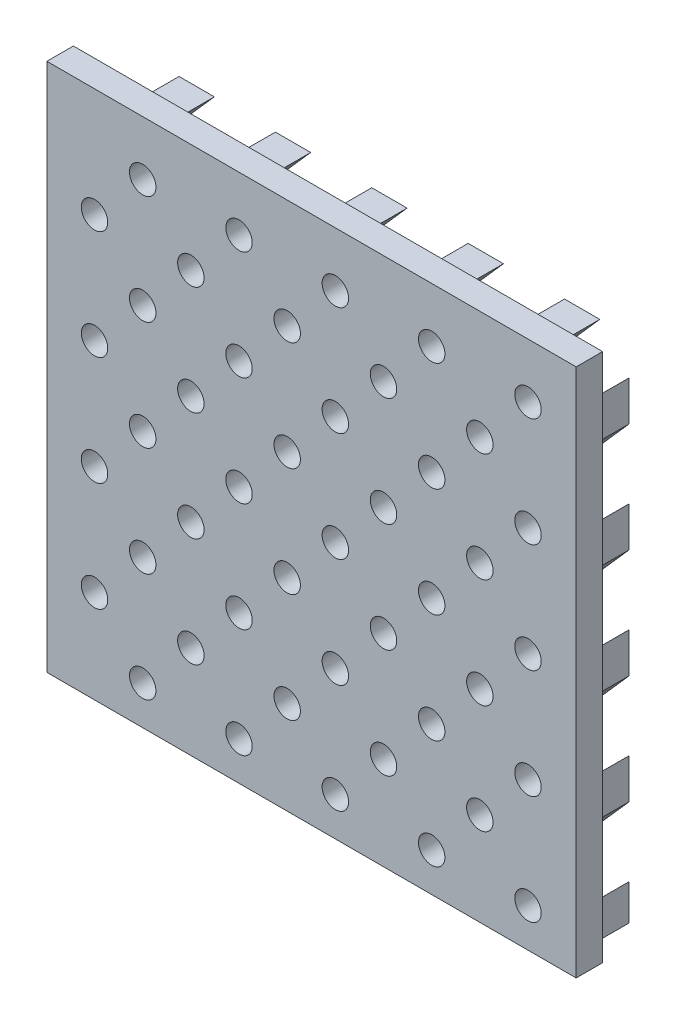
SolidWorks part; units mm, degrees
ref_plane "Front Plane" through (0, 0, 0) normal (0, 0, 1) x (1, 0, 0)
ref_plane "Top Plane" through (0, 0, 0) normal (0, 1, 0) x (1, 0, 0)
ref_plane "Right Plane" through (0, 0, 0) normal (1, 0, 0) x (0, 0, -1)
sketch "Sketch1" plane through (0, 0, 0) normal (0, 0, 1) x (1, 0, 0)
  line L1 (-100, 100) -> (100, 100)
  line L2 (-100, 100) -> (-100, -100)
  line L3 (-100, -100) -> (100, -100)
  line L4 (100, 100) -> (100, -100)
  line L5 (-100, 100) -> (100, -100) construction
  line L6 (-100, -100) -> (100, 100) construction
  point P0 (0, 0)
  dimension "D1" = 200
  dimension "D2" = 200
extrude "Boss-Extrude1" add sketch "Sketch1" along normal blind 5
sketch "Sketch2" plane through (0, 0, 0) normal (0, 0, -1) x (-1, 0, 0)
  circle A0 centre (-90.9, 89.7) radius 2.5
  circle A1 centre (-81.8, 79.4) radius 2.5
extrude "Cut-Extrude2" cut sketch "Sketch2" against normal blind 5
pattern_linear "LPattern1" count 10 spacing 18.2 along (-1, 0, 0) of "Cut-Extrude2"
sketch "Sketch3" plane through (0, 0, 0) normal (0, 0, -1) x (-1, 0, 0)
  circle A0 centre (91.1, 89.7) radius 2.5
extrude "Cut-Extrude3" cut sketch "Sketch3" against normal blind 5
pattern_linear "LPattern3" count 10 spacing 20.6 along (0, -1, 0) of "LPattern1", "Cut-Extrude3"
sketch "Sketch4" plane through (0, 0, 0) normal (0, 0, -1) x (-1, 0, 0)
  line L5 (68.35, -80.25) -> (85.799, -100)
  line L6 (100, -100) -> (-100, -100) construction
  line L7 (68.35, -80.25) -> (-90.9, 100)
  line L8 (-100, 100) -> (100, 100) construction
  line L10 (-80.9518, 92.5158) -> (-93.4841, 106.7007)
  line L11 (-82.8254, 90.8606) -> (-95.3576, 105.0455)
  line L12 (-93.4841, 106.7007) -> (-95.3576, 105.0455)
  line L14 (-84.8981, 89.4307) -> (-97.2312, 103.3902)
  line L15 (-83.0245, 91.086) -> (-95.3576, 105.0455)
  line L16 (-97.2312, 103.3902) -> (-95.3576, 105.0455)
  line L18 (-82.8254, 90.8606) -> (101.7199, -118.0203)
  line L19 (-80.9518, 92.5158) -> (103.5934, -116.3651)
  line L20 (101.7199, -118.0203) -> (103.5934, -116.3651)
  line L22 (-84.8981, 89.4307) -> (99.8464, -119.6756)
  line L23 (-83.0245, 91.086) -> (101.7199, -118.0203)
  line L24 (99.8464, -119.6756) -> (101.7199, -118.0203)
  point P10 (-80.9518, 92.5158)
  point P17 (-84.8981, 89.4307)
  point P18 (-78.918, 82.6621)
  point P25 (-75.582, 86.4379)
  dimension "D1" = 2.5
  dimension "D2" = 2.5
extrude "Boss-Extrude2" add sketch "Sketch4" along normal blind 7 contours L18 L20 L19 L10 L12 L11 L7 L5 | L22 L24 L18 L5 L7 L11 L16 L14 region at (-4.1179, -5.6598, 0) region at (-2.2444, -7.3151, 0)
sketch "Sketch5" plane through (0, 0, 0) normal (0, 0, -1) x (-1, 0, 0)
  line L0 (63.8, -85.4) -> (54.7, -75.1)
sketch "Sketch6" plane through (0, 0, 0) normal (0, 0, -1) x (-1, 0, 0)
  line L0 (54.7, -75.1) -> (45.6, -85.4)
pattern_linear "LPattern4" count 11 spacing 13.75 along (-0.6621, 0.7494, 0) of "Boss-Extrude2"
pattern_linear "LPattern5" count 11 spacing 13.75 along (0.6621, -0.7494, 0) of "LPattern4"
sketch "Sketch7" plane through (0, 0, -7) normal (0, 0, -1) x (-1, 0, 0)
  line L1 (100, 100) -> (213.2415, 100)
  line L2 (100, 100) -> (100, -126.1346)
  line L3 (100, -126.1346) -> (213.2415, -126.1346)
  line L4 (213.2415, 100) -> (213.2415, -126.1346)
extrude "Cut-Extrude4" cut sketch "Sketch7" against normal through all both and the other way through all
sketch "Sketch8" plane through (0, 0, 5) normal (0, 0, 1) x (1, 0, 0)
  line L1 (-100, -100) -> (119.6092, -100)
  line L2 (-100, -100) -> (-100, -230.9089)
  line L3 (-100, -230.9089) -> (119.6092, -230.9089)
  line L4 (119.6092, -100) -> (119.6092, -230.9089)
extrude "Cut-Extrude5" cut sketch "Sketch8" against normal through all both and the other way through all
sketch "Sketch9" plane through (0, 0, 5) normal (0, 0, 1) x (1, 0, 0)
  line L1 (100, -100) -> (215.7068, -100)
  line L2 (100, -100) -> (100, 118.5367)
  line L3 (100, 118.5367) -> (215.7068, 118.5367)
  line L4 (215.7068, -100) -> (215.7068, 118.5367)
extrude "Cut-Extrude6" cut sketch "Sketch9" against normal through all both and the other way through all
sketch "Sketch10" plane through (0, 0, 5) normal (0, 0, 1) x (1, 0, 0)
  line L1 (-100, 100) -> (125.7187, 100)
  line L2 (-100, 100) -> (-100, 218.908)
  line L3 (-100, 218.908) -> (125.7187, 218.908)
  line L4 (125.7187, 100) -> (125.7187, 218.908)
extrude "Cut-Extrude7" cut sketch "Sketch10" against normal through all both and the other way through all
sketch "Sketch11" plane through (0, 0, 0) normal (0, 0, -1) x (-1, 0, 0)
  line L0 (100, 100) -> (100, 98)
  line L1 (100, 100) -> (100, 93.7908) construction
  line L2 (100, 100) -> (100, 98)
  line L3 (100, 100) -> (-101.0177, 100)
  line L4 (100, 98) -> (-101.0177, 98)
  line L5 (-101.0177, 100) -> (-101.0177, 98)
  line M2 (94.5142, 100) -> (100, 93.7908)
extrude "Cut-Extrude8" cut sketch "Sketch11" along normal through all contours L3 L5 L4 M2 region at (2.8093, 98.9985, 0)
sketch "Sketch12" plane through (0, 0, 0) normal (0, 0, -1) x (-1, 0, 0)
  line L0 (-100, 100) -> (-98, 100)
  line L1 (-100, 100) -> (100, 100) construction
  line L2 (-100, 100) -> (-98, 100)
  line L3 (-100, 100) -> (-100, -101.7901)
  line L4 (-98, 100) -> (-98, -101.7901)
  line L5 (-100, -101.7901) -> (-98, -101.7901)
  line L6 (100, -100) -> (100, -98)
  line L7 (100, -100) -> (98, -100)
  line L8 (100, -100) -> (89.135, -100) construction
extrude "Cut-Extrude13" cut sketch "Sketch12" along normal through all contours L3 L5 L4 L0 region at (99, -0.8951, 0)
sketch "Sketch14" plane through (0, 0, 0) normal (0, 0, -1) x (-1, 0, 0)
  line L0 (-100, -100) -> (-100, -98)
  line L1 (-100, -100) -> (-100, 100) construction
  line L2 (-100, -100) -> (-100, -98)
  line L3 (-100, -100) -> (108.5797, -100)
  line L4 (-100, -98) -> (108.5797, -98)
  line L5 (108.5797, -100) -> (108.5797, -98)
extrude "Cut-Extrude15" cut sketch "Sketch14" along normal through all contours L3 L5 L4 L0 region at (-4.2899, -99, 0)
sketch "Sketch15" plane through (0, 0, 0) normal (0, 0, -1) x (-1, 0, 0)
  line L0 (100, -100) -> (98, -100)
  line L1 (100, -100) -> (-100, -100) construction
  line L2 (100, -100) -> (98, -100)
  line L3 (100, -100) -> (100, 113.5891)
  line L4 (98, -100) -> (98, 113.5891)
  line L5 (100, 113.5891) -> (98, 113.5891)
extrude "Cut-Extrude16" cut sketch "Sketch15" along normal through all contours L3 L5 L4 L0 region at (-99, 6.7945, 0)
sketch "Sketch16" plane through (0, 0, 0) normal (0, 0, -1) x (-1, 0, 0)
  line L0 (-100, 100) -> (0, 100)
  line L1 (-100, 100) -> (100, 100) construction
  line L2 (-100, 100) -> (-100, 0)
  line L3 (-100, -100) -> (-100, 100) construction
  line L4 (0, 100) -> (0, 0)
  line L5 (-100, 0) -> (0, 0)
  line L6 (-100, 0) -> (-100, -100)
  line L7 (-100, -100) -> (100, -100)
  line L8 (100, 100) -> (100, -100) construction
  line L9 (100, -100) -> (-100, -100) construction
  line L10 (100, -100) -> (100, 100)
  line L11 (100, 100) -> (0, 100)
extrude "Cut-Extrude17" cut sketch "Sketch16" against normal through all both and the other way through all contours L10 L11 L4 L5 L6 L7 region at (-16.6667, -16.6667, 0)
sketch "Sketch17" plane through (0, 0, 0) normal (0, 0, -1) x (-1, 0, 0)
  line L0 (0, 92.198) -> (0, 96.3816) construction
  line L1 (0, 94.2898) -> (-2.5136, 94.2898)
  line L2 (0, 94.2898) -> (0, 4.6608)
  line L3 (0, 4.6608) -> (-2.5136, 4.6608)
  line L4 (-2.5136, 94.2898) -> (-2.5136, 4.6608)
extrude "Boss-Extrude3" add sketch "Sketch17" against normal blind 5
sketch "Sketch20" plane through (0, 0, -7) normal (0, 0, -1) x (-1, 0, 0)
  line L0 (0, 0) -> (-2, 0)
  line L1 (-5.8864, 0) -> (0, 0) construction
  line L2 (-2, 0) -> (-2, 100)
  line L3 (0, 0) -> (0, 100)
  line L4 (-2, 100) -> (0, 100)
extrude "Cut-Extrude18" cut sketch "Sketch20" against normal blind 7
sketch "Sketch21" plane through (0, 0, -7) normal (0, 0, -1) x (-1, 0, 0)
  line L0 (-2, 0) -> (-2, 2)
  line L1 (-2, 3.1528) -> (-2, 0) construction
  line L2 (-2, 2) -> (-99.4221, 2)
  line L3 (-99.4221, 2) -> (-99.4221, 0)
  line L4 (-99.4221, 0) -> (-2, 0)
  line L5 (-2, 0) -> (-2.0032, -0.0316)
  line M1 (-2, 0) -> (-2, 3.1528)
  line M4 (-92.469, 98) -> (-5.8864, 0)
  line M5 (-5.8864, 0) -> (-2, 0)
extrude "Cut-Extrude19" cut sketch "Sketch21" against normal blind 7 contours L2 M1 M4 M5 | L3 L4 L2 M4 region at (4.4122, 1.0617, -7) region at (53.0946, 0.9968, -7)
